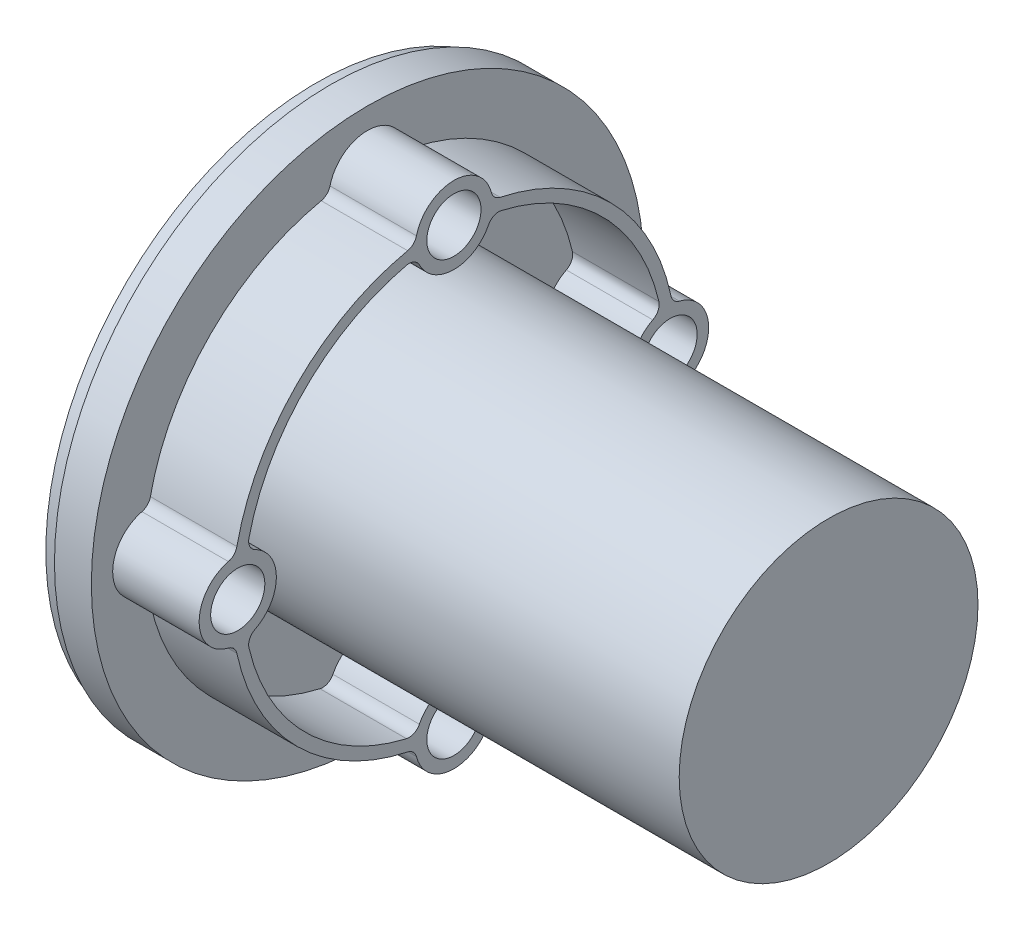
SolidWorks part; units mm, degrees
ref_plane "Front Plane" through (0, 0, 0) normal (0, 0, 1) x (1, 0, 0)
ref_plane "Top Plane" through (0, 0, 0) normal (0, 1, 0) x (1, 0, 0)
ref_plane "Right Plane" through (0, 0, 0) normal (1, 0, 0) x (0, 0, -1)
sketch "Sketch1" plane through (0, 0, 0) normal (1, 0, 0) x (0, 0, -1)
  circle A0 centre (0, 0) radius 25.0825
  dimension "D1" = 50.165
extrude "Extrude-Thin1" add sketch "Sketch1" along normal blind 21.59 thin thin type one direction wall 3.81
sketch "Sketch2" plane through (21.59, 0, 0) normal (1, 0, 0) x (0, 0, -1)
  circle A0 centre (0, 0) radius 59.563
  dimension "D1" = 119.126
extrude "Boss-Extrude1" add sketch "Sketch2" against normal blind 3.175 separate body
sketch "Sketch3" plane through (18.415, 0, 0) normal (-1, 0, 0) x (0, 0, 1)
  line L0 (35.687, 0) -> (47.625, 0) construction
  line L1 (35.687, 5.969) -> (47.625, 5.969)
  line L2 (35.687, -5.969) -> (47.625, -5.969)
  line L3 (-5.969, -35.687) -> (-5.969, -47.625)
  line L4 (5.969, -35.687) -> (5.969, -47.625)
  line L5 (0, -35.687) -> (0, -47.625) construction
  line L6 (-35.687, 5.969) -> (-47.625, 5.969)
  line L7 (-35.687, -5.969) -> (-47.625, -5.969)
  line L8 (-35.687, 0) -> (-47.625, 0) construction
  line L9 (5.969, 35.687) -> (5.969, 47.625)
  line L10 (-5.969, 35.687) -> (-5.969, 47.625)
  line L11 (0, 35.687) -> (0, 47.625) construction
  arc A0 (35.687, 5.969) -> (35.687, -5.969) centre (35.687, 0) ccw
  arc A1 (47.625, -5.969) -> (47.625, 5.969) centre (47.625, 0) ccw
  arc A2 (5.969, -35.687) -> (-5.969, -35.687) centre (0, -35.687) ccw
  arc A3 (-5.969, -47.625) -> (5.969, -47.625) centre (0, -47.625) ccw
  arc A4 (-35.687, -5.969) -> (-35.687, 5.969) centre (-35.687, 0) ccw
  arc A5 (-47.625, 5.969) -> (-47.625, -5.969) centre (-47.625, 0) ccw
  arc A6 (-5.969, 35.687) -> (5.969, 35.687) centre (0, 35.687) ccw
  arc A7 (5.969, 47.625) -> (-5.969, 47.625) centre (0, 47.625) ccw
  point P3 (41.656, 0)
  point P13 (0, -41.656)
  point P20 (-41.656, 0)
  point P27 (0, 41.656)
  point P32 (0, 0)
  dimension "D2" = 5.969
  dimension "D1" = 47.625
  dimension "D3" = 11.938
  dimension "D4" = 4
extrude "Cut-Extrude1" cut sketch "Sketch3" against normal through all
sketch "Sketch4" plane through (21.59, 0, 0) normal (1, 0, 0) x (0, 0, -1)
  circle A0 centre (0, 0) radius 60.833
  dimension "D1" = 121.666
extrude "Boss-Extrude2" add sketch "Sketch4" along normal blind 8.128 separate body
sketch "Sketch5" plane through (18.415, 0, 0) normal (-1, 0, 0) x (0, 0, 1)
  circle A0 centre (0, 0) radius 25.0825 construction
  circle A1 centre (0, 0) radius 25.0825
  arc A2 (-5.969, -47.625) -> (5.969, -47.625) centre (0, -47.625) ccw construction
  arc A3 (47.625, -5.969) -> (47.625, 5.969) centre (47.625, 0) ccw construction
  arc A4 (-47.625, 5.969) -> (-47.625, -5.969) centre (-47.625, 0) ccw construction
  arc A5 (5.969, 47.625) -> (-5.969, 47.625) centre (0, 47.625) ccw construction
  arc A6 (-5.969, -47.625) -> (5.969, -47.625) centre (0, -47.625) ccw
  arc A7 (47.625, -5.969) -> (47.625, 5.969) centre (47.625, 0) ccw
  arc A8 (-47.625, 5.969) -> (-47.625, -5.969) centre (-47.625, 0) ccw
  arc A9 (5.969, 47.625) -> (-5.969, 47.625) centre (0, 47.625) ccw
  circle A10 centre (0, 47.625) radius 5.969
  circle A11 centre (47.625, 0) radius 5.969
  circle A12 centre (-47.625, 0) radius 5.969
  circle A13 centre (0, -47.625) radius 5.969
  arc M4 (47.625, 5.969) -> (47.625, -5.969) centre (47.625, 0) cw
  arc M8 (5.969, -47.625) -> (-5.969, -47.625) centre (0, -47.625) cw
  arc M12 (-47.625, -5.969) -> (-47.625, 5.969) centre (-47.625, 0) cw
  arc M16 (-5.969, 47.625) -> (5.969, 47.625) centre (0, 47.625) cw
extrude "Cut-Extrude2" cut sketch "Sketch5" against normal through all contours A12 M12 | A10 M16 | A11 M4 | A13 M8 | A1 region at (18.415, 0, 0) region at (18.415, -47.625, 0) region at (18.415, 0, 47.625) region at (18.415, 0, -47.625) region at (18.415, 47.625, 0)
sketch "Sketch6" plane through (29.718, 0, 0) normal (1, 0, 0) x (0, 0, -1)
  circle A0 centre (-47.625, 0) radius 5.969 construction
  circle A1 centre (-47.625, 0) radius 5.969
  circle A2 centre (-47.625, 0) radius 8.509
  arc A3 (-47.625, 0) -> (0, 47.625) centre (0, 0) cw construction
  arc A4 (-46.355, 0) -> (0, 46.355) centre (0, 0) cw
  arc A5 (-48.895, 0) -> (0, 48.895) centre (0, 0) cw
  arc A6 (0, 46.355) -> (46.355, 0) centre (0, 0) cw
  arc A7 (0, 48.895) -> (48.895, 0) centre (0, 0) cw
  circle A8 centre (0, 47.625) radius 8.509
  circle A9 centre (0, 47.625) radius 5.969
  arc A10 (46.355, 0) -> (0, -46.355) centre (0, 0) cw
  arc A11 (48.895, 0) -> (0, -48.895) centre (0, 0) cw
  circle A12 centre (47.625, 0) radius 8.509
  circle A13 centre (47.625, 0) radius 5.969
  arc A14 (0, -46.355) -> (-46.355, 0) centre (0, 0) cw
  arc A15 (0, -48.895) -> (-48.895, 0) centre (0, 0) cw
  circle A16 centre (0, -47.625) radius 8.509
  circle A17 centre (0, -47.625) radius 5.969
  point P41 (0, 0)
  circle M3 centre (0, 47.625) radius 5.969
  circle M4 centre (0, -47.625) radius 5.969
  circle M7 centre (-47.625, 0) radius 5.969
  circle M8 centre (47.625, 0) radius 5.969
  dimension "D1" = 2.54
  dimension "D2" = 1.27
  dimension "D3" = 2.54
  dimension "D4" = 4
extrude "Boss-Extrude4" add sketch "Sketch6" along normal blind 19.05 separate body contours A14 A2 A4 M7 | A2 A15 A5 M7 | A5 A1 A4 A2 | A8 A5 A2 A4 | A15 A2 A14 A1 | A16 A14 A2 A15 | A5 A8 A4 M3 | A7 A8 A5 M3 | A4 A8 A6 M3 | A6 A8 A7 M3 | A12 A7 A8 A6 | A7 A12 A6 M8 | A6 A12 A10 M8 | A11 A12 A7 M8 | A10 A12 A11 M8 | A16 A11 A12 A10 | A10 A16 A14 M4 | A14 A16 A15 M4 | A15 A16 A11 M4 | A11 A16 A10 M4 region at (29.718, 3.7078, 42.7208) region at (29.718, 7.1797, 47.0806) region at (29.718, -7.1797, 47.0806) region at (29.718, 0, 53.7817) region at (29.718, 9.0376, 46.8235) region at (29.718, -33.1768, 33.1768) region at (29.718, 47.0806, 7.1797) region at (29.718, 45.6452, 6.9808) region at (29.718, -39.2951, 0) region at (29.718, -47.0806, 7.1797) region at (29.718, 55.9463, 0) region at (29.718, 46.544, -9.0084) region at (29.718, 47.0806, -7.1797) region at (29.718, -48.5479, 7.2259) region at (29.718, -47.0806, -7.1797) region at (29.718, -33.1768, -33.1768) region at (29.718, 7.1797, -47.0806) region at (29.718, 6.9808, -45.6452) region at (29.718, -7.1797, -47.0806) region at (29.718, 5.699, -53.6885)
fillet "Fillet1" radius 2.54 16 edges at (39.243, -8.2674, 45.6118) (39.243, 8.2674, 45.6118) (39.243, -8.4927, 48.1518) (39.243, 8.4927, 48.1518) (39.243, -48.1518, 8.4927) (39.243, -48.1518, -8.4927) (39.243, -8.4927, -48.1518) (39.243, 8.2674, -45.6118) (39.243, 48.1518, -8.4927) (39.243, 48.1518, 8.4927) (39.243, -45.6118, -8.2674) (39.243, -45.6118, 8.2674) (39.243, -8.2674, -45.6118) (39.243, 8.4927, -48.1518) (39.243, 45.6118, 8.2674) (39.243, 45.6118, -8.2674)
sketch "Sketch7" plane through (29.718, 0, 0) normal (1, 0, 0) x (0, 0, -1)
  circle A0 centre (0, 0) radius 32.9184
  dimension "D1" = 65.8368
extrude "Boss-Extrude5" add sketch "Sketch7" along normal blind 101.6
sketch "Sketch8" plane through (29.718, 0, 0) normal (-1, 0, 0) x (0, 0, 1)
  circle A0 centre (0, 0) radius 10.795
  dimension "D1" = 21.59
extrude "Boss-Extrude6" add sketch "Sketch8" along normal up to surface (29.718 mm away) up to face at (0, 0, -28.8925)
chamfer "Chamfer1" distance 1.27 angle 45 2 edges at (0, 0, -10.795) (0, 0, -28.8925)
